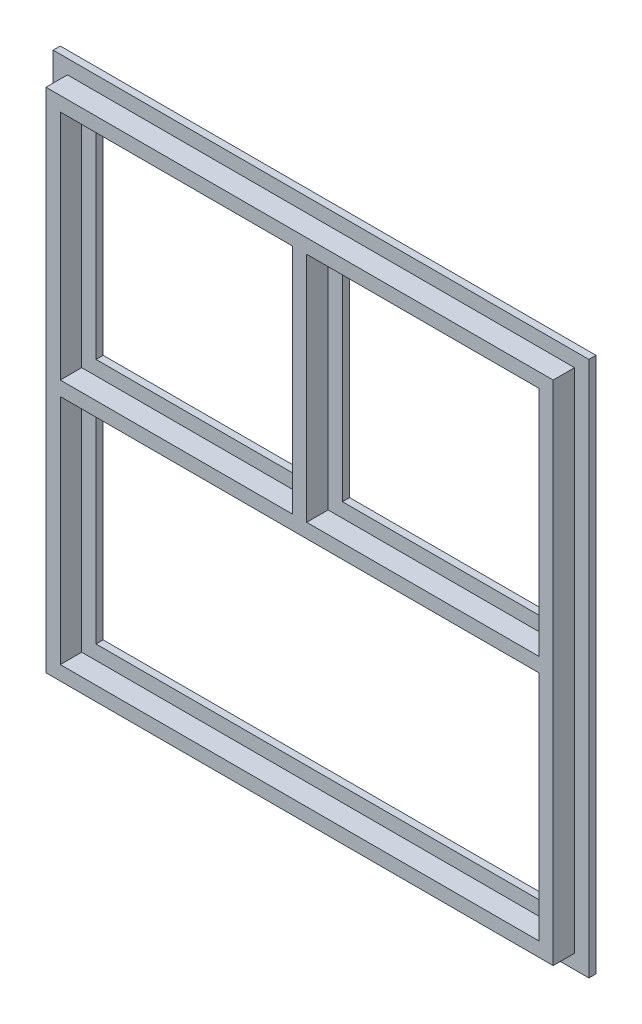
SolidWorks part; units mm, degrees
ref_plane "Plano frontal" through (0, 0, 0) normal (0, 0, 1) x (1, 0, 0)
ref_plane "Plano superior" through (0, 0, 0) normal (0, 1, 0) x (1, 0, 0)
ref_plane "Plano direito" through (0, 0, 0) normal (1, 0, 0) x (0, 0, -1)
sketch "Esboço1" plane through (0, 0, 0) normal (0, 0, 1) x (1, 0, 0)
  line L1 (-37.5, -37.5) -> (37.5, -37.5)
  line L2 (-37.5, -37.5) -> (-37.5, 37.5)
  line L3 (-37.5, 37.5) -> (37.5, 37.5)
  line L4 (37.5, -37.5) -> (37.5, 37.5)
  line L5 (-37.5, -37.5) -> (37.5, 37.5) construction
  line L6 (-37.5, 37.5) -> (37.5, -37.5) construction
  point P0 (0, 0)
  dimension "D1" = 75
  dimension "D2" = 75
extrude "Ressalto-extrusão1" add sketch "Esboço1" along normal blind 1
sketch "Esboço2" plane through (0, 0, 1) normal (0, 0, 1) x (1, 0, 0)
  line L1 (-35.5, -35.5) -> (35.5, -35.5)
  line L2 (-35.5, -35.5) -> (-35.5, 35.5)
  line L3 (-35.5, 35.5) -> (35.5, 35.5)
  line L4 (35.5, -35.5) -> (35.5, 35.5)
  line L5 (-35.5, -35.5) -> (35.5, 35.5) construction
  line L6 (-35.5, 35.5) -> (35.5, -35.5) construction
  line L7 (-33.5, -33.5) -> (33.5, -33.5)
  line L8 (-33.5, -33.5) -> (-33.5, 33.5)
  line L9 (-33.5, 33.5) -> (33.5, 33.5)
  line L10 (33.5, -33.5) -> (33.5, 33.5)
  line L11 (-33.5, -33.5) -> (33.5, 33.5) construction
  line L12 (-33.5, 33.5) -> (33.5, -33.5) construction
  point P0 (0, 0)
  point P6 (0, 0)
  dimension "D1" = 71
  dimension "D2" = 71
  dimension "D3" = 2
  dimension "D4" = 2
extrude "Ressalto-extrusão2" add sketch "Esboço2" along normal blind 3
sketch "Esboço3" plane through (0, 0, 1) normal (0, 0, 1) x (1, 0, 0)
  line L0 (-33.5, 33.5) -> (-33.5, -33.5) construction
  line L1 (3, 14.75) -> (3, 3)
  line L2 (33.5, -33.5) -> (33.5, 33.5) construction
  line L3 (3, 3) -> (15.75, 3)
  line L4 (0, -3) -> (0, 32.5)
  line L6 (33.5, 33.5) -> (-33.5, 33.5) construction
  line L7 (3, 3) -> (31.5, 3)
  line L8 (0, -3) -> (31.5, -3)
  line L9 (15.75, -3) -> (15.75, 3)
  line L10 (3, 3) -> (3, 31.5)
  line L11 (3, 31.5) -> (31.5, 31.5)
  line L16 (-33.5, -33.5) -> (33.5, -33.5) construction
  line L21 (-31.5, -3) -> (31.5, -3)
  line L22 (-31.5, -3) -> (-31.5, -31.5)
  line L23 (-31.5, -31.5) -> (31.5, -31.5)
  line L24 (31.5, -3) -> (31.5, -31.5)
  line L26 (0, 14.75) -> (3, 14.75)
  line L27 (0, 14.75) -> (-3, 14.75)
  line L28 (-31.5, -3) -> (0, -3)
  line L29 (-31.5, -3) -> (0, -3)
  line L30 (-17.25, 3) -> (-17.25, -3)
  line L31 (31.5, 3) -> (31.5, 31.5)
  line L32 (-3, 3) -> (-31.5, 3)
  line L33 (-3, 3) -> (-3, 31.5)
  line L34 (-3, 31.5) -> (-31.5, 31.5)
  line L35 (-31.5, 3) -> (-31.5, 31.5)
  dimension "D2" = 2
  dimension "D3" = 2
  dimension "D4" = 3
  dimension "D5" = 3
  dimension "D6" = 6
  dimension "D7" = 2
  dimension "D8" = 2
  dimension "D9" = 2
  dimension "D10" = 2
  dimension "D11" = 2
  dimension "D12" = 28.5
  dimension "D13" = 6
extrude "Corte-extrusão2" cut sketch "Esboço3" against normal blind 3 contours L24 L21 L22 L23 | L33 L32 L35 L34 | L10 L7 L31 L11 region at (0, -17.25, 1)
sketch "Esboço4" plane through (0, 0, 1) normal (0, 0, 1) x (1, 0, 0)
  line L0 (-33.5, 33.5) -> (33.5, 33.5)
  line L3 (33.5, -33.5) -> (33.5, 33.5) construction
  line L5 (-33.5, 33.5) -> (-33.5, -33.5) construction
  line L6 (-33.5, 0) -> (-33.5, 1)
  line L7 (-33.5, 0) -> (-33.5, -1)
  line L8 (-33.5, 33.5) -> (-33.5, -33.5) construction
  line L9 (0, 33.5) -> (-1, 33.5)
  line L10 (0, 33.5) -> (1, 33.5)
  line L11 (33.5, 0) -> (33.5, 1)
  line L12 (33.5, -33.5) -> (33.5, 33.5) construction
  line L13 (33.5, 0) -> (33.5, -1)
  line L14 (33.5, 1) -> (1, 1)
  line L15 (1, 1) -> (1, 33.5)
  line L16 (-1, 33.5) -> (-1, 1)
  line L17 (-1, 1) -> (-33.5, 1)
  line L18 (-33.5, -1) -> (33.5, -1)
  line M10 (33.5, -33.5) -> (33.5, 33.5)
  line M12 (-33.5, 33.5) -> (-33.5, -33.5)
  dimension "D1" = 1
  dimension "D2" = 1
  dimension "D3" = 1
  dimension "D4" = 1
  dimension "D5" = 1
  dimension "D6" = 1
extrude "Ressalto-extrusão3" add sketch "Esboço4" along normal blind 3 contours L18 L14 L15 L0 L16 L17 M12 M10 region at (0, 5.6344, 1)
